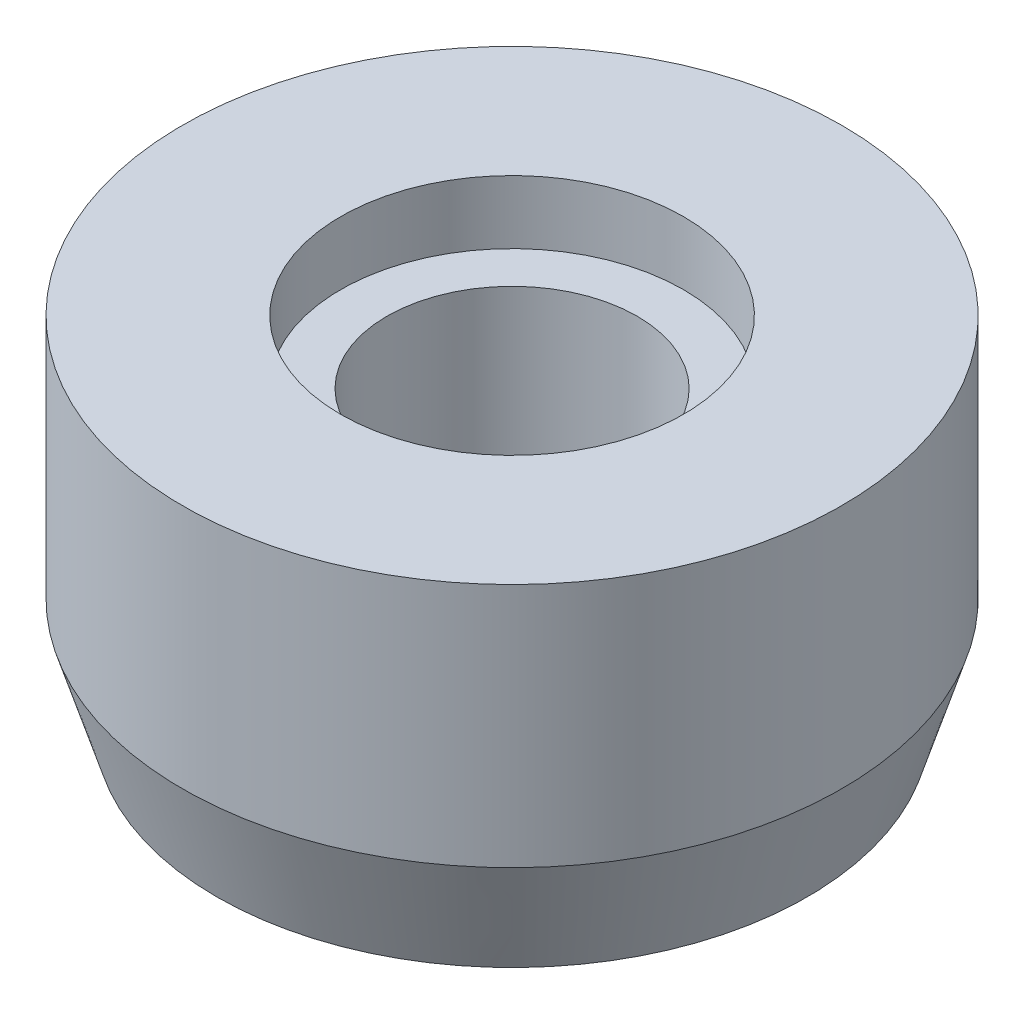
SolidWorks part; units mm, degrees
material "BUTYL"
ref_plane "Front Plane" through (0, 0, 0) normal (0, 0, 1) x (1, 0, 0)
ref_plane "Top Plane" through (0, 0, 0) normal (0, 1, 0) x (1, 0, 0)
ref_plane "Right Plane" through (0, 0, 0) normal (1, 0, 0) x (0, 0, -1)
sketch "Sketch1" plane through (0, 0, 0) normal (0, 0, 1) x (1, 0, 0)
  line L0 (0, -13.5) -> (0, 0) construction
  line L1 (0, 0) -> (12.5, 0) construction
  line L2 (12.5, 0) -> (6.5, 0)
  line L3 (6.5, 0) -> (6.5, -2.4)
  line L4 (6.5, -2.4) -> (4.75, -2.4)
  line L5 (4.75, -2.4) -> (4.75, -13.5)
  line L6 (4.75, -13.5) -> (11.2, -13.5)
  line L7 (11.2, -13.5) -> (12.5, -9.3)
  line L8 (12.5, -9.3) -> (12.5, 0)
  dimension "D1" = 13.5
  dimension "D2" = 12.5
  dimension "D3" = 2.4
  dimension "D4" = 6
  dimension "D5" = 4.2
  dimension "D6" = 1.3
  dimension "D7" = 4.75
revolve "Revolve1" add sketch "Sketch1" angle 360 about L0
